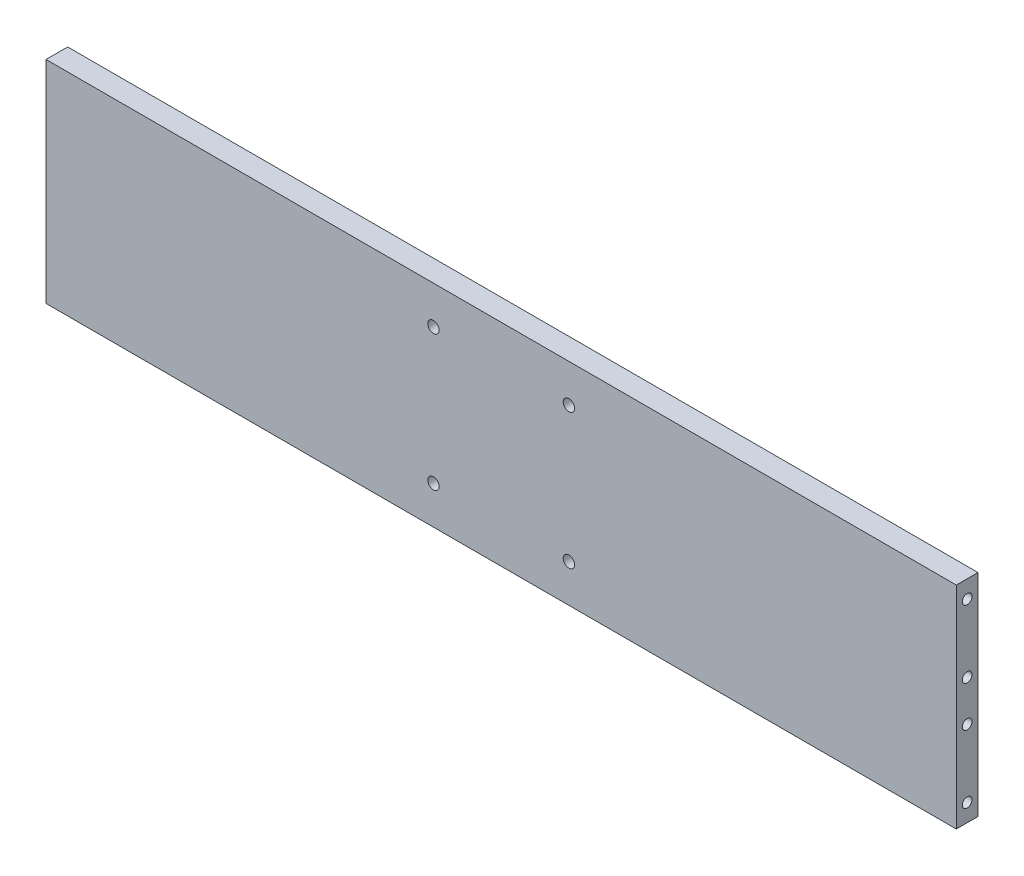
SolidWorks part; units mm, degrees
ref_plane "Front Plane" through (0, 0, 0) normal (0, 0, 1) x (1, 0, 0)
ref_plane "Top Plane" through (0, 0, 0) normal (0, 1, 0) x (1, 0, 0)
ref_plane "Right Plane" through (0, 0, 0) normal (1, 0, 0) x (0, 0, -1)
sketch "Sketch1" plane through (0, 0, 0) normal (0, 0, 1) x (1, 0, 0)
  line L1 (-168, -39) -> (168, -39)
  line L2 (-168, -39) -> (-168, 39)
  line L3 (-168, 39) -> (168, 39)
  line L4 (168, -39) -> (168, 39)
  line L5 (-168, -39) -> (168, 39) construction
  line L6 (-168, 39) -> (168, -39) construction
  line L7 (-25, -25) -> (25, -25) construction
  line L8 (-25, -25) -> (-25, 25) construction
  line L9 (-25, 25) -> (25, 25) construction
  line L10 (25, -25) -> (25, 25) construction
  line L11 (-25, -25) -> (25, 25) construction
  line L12 (-25, 25) -> (25, -25) construction
  circle A0 centre (-25, 25) radius 2.1
  circle A1 centre (25, 25) radius 2.1
  circle A2 centre (25, -25) radius 2.1
  circle A3 centre (-25, -25) radius 2.1
  point P0 (0, 0)
  point P6 (0, 0)
  dimension "D1" = 336
  dimension "D2" = 78
  dimension "D3" = 50
  dimension "D4" = 50
extrude "Boss-Extrude1" add sketch "Sketch1" along normal blind 8
sketch "Sketch2" plane through (168, 0, 0) normal (1, 0, 0) x (0, 0, -1)
  line L0 (-8, 0) -> (0, 0) construction
  line L1 (-8, -39) -> (-8, 39) construction
  line L2 (0, -39) -> (0, 39) construction
  line L3 (-4, 39) -> (-4, 0) construction
  line L4 (-8, 39) -> (0, 39) construction
  circle A0 centre (-4, 32.5) radius 1.8
  circle A1 centre (-4, 7.5) radius 1.8
  circle A2 centre (-4, -7.5) radius 1.8
  circle A3 centre (-4, -32.5) radius 1.8
  point P14 (-4, 19.5)
  dimension "D1" = 25
  dimension "D2" = 7.5
extrude "Cut-Extrude1" cut sketch "Sketch2" against normal up to next
